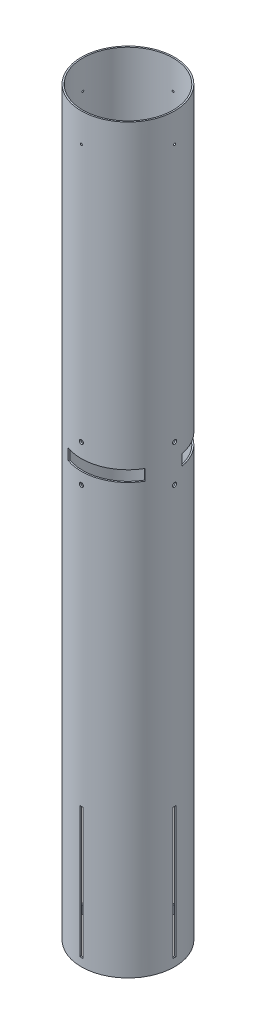
SolidWorks part; units mm, degrees
material "A-Glass Fiber"
ref_plane "Front Plane" through (0, 0, 0) normal (0, 0, 1) x (1, 0, 0)
ref_plane "Top Plane" through (0, 0, 0) normal (0, 1, 0) x (1, 0, 0)
ref_plane "Right Plane" through (0, 0, 0) normal (1, 0, 0) x (0, 0, -1)
sketch "Sketch1" plane through (0, 0, 0) normal (0, 1, 0) x (1, 0, 0)
  circle A0 centre (0, 0) radius 49.53
  circle A1 centre (0, 0) radius 51.1048
  dimension "D1" = 99.06
  dimension "D2" = 102.2096
extrude "Boss-Extrude1" add sketch "Sketch1" along normal blind 812.8
ref_plane "Plane1" through (0, 0, 0) normal (0.7071, 0, 0.7071) x (0.7071, 0, -0.7071)
ref_axis "Axis1" through (0, 812.8, 0) along (0, -1, 0)
sketch "Sketch2" plane through (0, 0, 0) normal (1, 0, 0) x (0, 0, -1)
  line L0 (0, 0) -> (0, 8.89)
  line L1 (1.5875, 8.89) -> (-1.5875, 8.89)
  line L2 (1.5875, 8.89) -> (1.5875, 152.4)
  line L3 (1.5875, 152.4) -> (-1.5875, 152.4)
  line L4 (-1.5875, 8.89) -> (-1.5875, 152.4)
  line L5 (1.5875, 8.89) -> (-1.5875, 152.4) construction
  line L6 (1.5875, 152.4) -> (-1.5875, 8.89) construction
  line L7 (51.1048, 812.8) -> (-51.1048, 812.8) construction
  line L8 (51.1048, 812.8) -> (-51.1048, 812.8)
  line L9 (0, 812.8) -> (0, 498.475)
  line L10 (-51.1048, 0) -> (51.1048, 0) construction
  circle A0 centre (0, 498.475) radius 2.25
  point P0 (0, 80.645)
  dimension "D4" = 4.5
  dimension "D1" = 3.175
  dimension "D5" = 498.475
  dimension "D3" = 152.4
  dimension "D2" = 8.89
extrude "Cut-Extrude1" cut sketch "Sketch2" against normal through all contours L4 L1 L2 L3 region at (0, 80.645, 0)
pattern_circular "CirPattern1" count 4 over 360 about axis through (0, 0, 0) along (0, 1, 0) of "Cut-Extrude1" reverse direction yes
extrude "Cut-Extrude2" cut sketch "Sketch2<3>" against normal through all contours A0 region at (0, 496.929, 1.546)
sketch "Sketch2<3>" plane through (0, 0, 0) normal (1, 0, 0) x (0, 0, -1) same geometry as "Sketch2"
pattern_circular "CirPattern2" count 4 over 360 about axis through (0, 812.8, 0) along (0, -1, 0) of "Cut-Extrude2"
sketch "Sketch3" plane through (0, 0, 0) normal (0.7071, 0, 0.7071) x (0.7071, 0, -0.7071)
  line L0 (0, 0) -> (0, 127) construction
  circle A0 centre (0, 127) radius 3.175
  dimension "D1" = 6.35
  dimension "D2" = 127
extrude "Cut-Extrude3" cut sketch "Sketch3" against normal through all
sketch "Sketch7" plane through (0, 0, 0) normal (0, 1, 0) x (1, 0, 0)
  line L0 (0, 0) -> (-44.2581, -25.5524)
  line L1 (0, 0) -> (0, 93.232) construction
  line L2 (0, 0) -> (-32.8495, 39.1485)
  line L3 (-51.1048, 0) -> (0, 0) construction
  arc A0 (-51.0552, 2.25) -> (-51.0552, -2.25) centre (0, 0) ccw construction
  circle A1 centre (0, 0) radius 49.53 construction
  circle A2 centre (0, 0) radius 51.1048
  circle A3 centre (0, 0) radius 51.1048
  circle A4 centre (0, 0) radius 49.53
  circle A5 centre (0, 0) radius 51.1048 construction
  arc A6 (2.25, 51.0552) -> (-2.25, 51.0552) centre (0, 0) ccw construction
  arc A7 (-51.0552, 2.25) -> (-51.0552, -2.25) centre (0, 0) ccw
  arc A8 (2.25, 51.0552) -> (-2.25, 51.0552) centre (0, 0) ccw
  dimension "D1" = 80
  dimension "D3" = 30
  dimension "D2" = 0
extrude "Cut-Extrude4" cut sketch "Sketch7" against normal blind 12.065 from offset 482.6 contours A4 A3 L0 region at (-43.9137, 0, 24.5741)
pattern_circular "CirPattern3" count 3 over 360 about axis through (0, 812.8, 0) along (0, -1, 0) of "Cut-Extrude4"
pattern_linear "LPattern1" count 2 spacing 40.7416 along (0, -1, 0) of "CirPattern2"
sketch "Sketch8" plane through (0, 0, 0) normal (0, 0, 1) x (1, 0, 0)
  line L0 (49.53, 812.8) -> (-49.53, 812.8) construction
  circle A0 centre (0, 781.05) radius 1.0922
  dimension "D1" = 2.1844
  dimension "D2" = 31.75
extrude "Cut-Extrude5" cut sketch "Sketch8" against normal through all
pattern_circular "CirPattern4" count 4 over 360 about axis through (0, 812.8, 0) along (0, -1, 0) of "Cut-Extrude5"
sketch "Sketch9" plane through (0, 0, 0) normal (0, 0, 1) x (1, 0, 0)
  line L0 (51.1048, 812.8) -> (-51.1048, 812.8) construction
  point P0 (0, 752.856)
  dimension "D1" = 59.944
hole_wizard "1/2 Clearance Hole4" positions "Sketch17" profile "Sketch18" hole size "1/2" standard "ANSI Inch" end condition through all
sketch "Sketch17" plane through (0, 0, 0) normal (0, 0, 1) x (1, 0, 0)
  line L0 (51.1048, 812.8) -> (-51.1048, 812.8) construction
  point P0 (0, 752.856)
  dimension "D1" = 752.856
  dimension "D2" = 59.944
sketch "Sketch18" plane through (0, 752.856, 0) normal (1, 0, 0) x (0, -1, 0)
  line L0 (0, 0) -> (0, 51.1048)
  line L1 (0, 51.1048) -> (6.5481, 51.1048)
  line L2 (6.5481, 51.1048) -> (6.5481, 0)
  line L5 (6.5481, 0) -> (0, 0)
  line L11 (0, -6.35) -> (0, 107.95) construction
  dimension "Thru Hole Dia." = 13.0962
  dimension "Thru Hole Depth" = 51.1048
ref_plane "Plane3" through (24.3888, 0, -29.0654) normal (0.6428, 0, -0.766) x (-0.766, 0, -0.6428)
equation "\"D1@Boss-Extrude1\" = \"Aft_Section_Length\""
equation "\"AB_Coupler_OD_Length\"= 1in"
equation "\"AB_Coupling_Section_Length\"= 0.375in"
equation "\"AB_Coupler_Length\"= \"AB_Coupler_OD_Length\" + \"AB_Coupling_Section_Length\" * 2"
equation "\"AB_Coupler_Num_Screws\"= 4"
equation "\"AB_Coupling_Screw_Diameter\"= 4.5mm"
equation "\"Aft_Section_Length\" = 32in"
equation "\"D4@Sketch2\"=\"AB_Coupling_Screw_Diameter\""
equation "\"D1@CirPattern2\"=\"AB_Coupler_Num_Screws\""
equation "\"Rail_Nut_From_Bottom\"= 5in"
equation "\"Rail_Nut_Diam\"= 0.25in"
equation "\"D1@Sketch3\"=\"Rail_Nut_Diam\""
equation "\"D2@Sketch3\"=\"Rail_Nut_From_Bottom\""
equation "\"AB_BKHD_Thickness\"= 0.375in"
equation "\"AB_Mount_From_Bottom\"= 19.25in"
equation "\"Cutout_Angle\" = 60"
equation "\"Motor_OD\" = 54.4mm"
equation "\"Motor_Length\" = 401mm"
equation "\"Mid_Coupler_Length\" = 12in"
equation "\"AB_Paddle_Height\" = 0.375in"
equation "\"Num_Cutouts\" = 4"
equation "\"AB_Coupler_OD\"= 4.024in"
equation "\"AB_Coupler_ID\"= 3.7in"
equation "\"AB_Coupler_Surface_Diameter\"= 3.899in"
equation "\"AB_Central_Bushing_Length\" = 0.75in"
equation "\"Lead_Screw_Dist\" = 2in"
equation "\"Lead_Screw_Diam\" = 0.375in"
equation "\"Lead_Screw_Length\" = \"Mid_Coupler_Length\" + 2*0.375in + 2*0.5in"
equation "\"Paddle_Pin_Offset\" = 0.25in"
equation "\"Paddle_Pin_Radius\" = 2.25*2/3in"
equation "\"Paddle_Gear_OD\" = 3.2in"
equation "\"Fwd_BKHD_From_Top\" = 18in"
equation "\"Body_Tube_OD\"= 4.024in"
equation "\"Body_Tube_ID\"= 3.90in"
equation "\"Coupler_OD\" = 3.899in"
equation "\"Coupler_ID\" = 3.755in"
equation "\"Fwd_Section_Length\" = 20in"
equation "\"Mid_Section_Length\" = 4in"
equation "\"Aft_Upper_Tube_Length\" = 10in"
equation "\"Aft_Lower_Tube_Length\" = 18in"
equation "\"Nosecone_Coupler_Length\" = 5in"
equation "\"Avionics_Bulkhead_Thickness\" = 0.25in"
equation "\"Avionics_Bulkhead_Lip\" = 0.125in"
equation "\"Avionics_Board_Length\" = \"Mid_Coupler_Length\" - 2*\"Avionics_Bulkhead_Lip\""
equation "\"Lead_Screw_Hole_Diam\" = 0.386in"
equation "\"Centering_Ring_Cutout_Dia\"= 1in"
equation "\"D2@Sketch1\"=\"Body_Tube_OD\""
equation "\"D1@Sketch1\"=\"Body_Tube_ID\""
equation "\"D5@Sketch2\"=\"AB_Mount_From_Bottom\"+0.375"
equation "\"D19@Cut-Extrude4\"=\"AB_Mount_From_Bottom\"-0.25"
